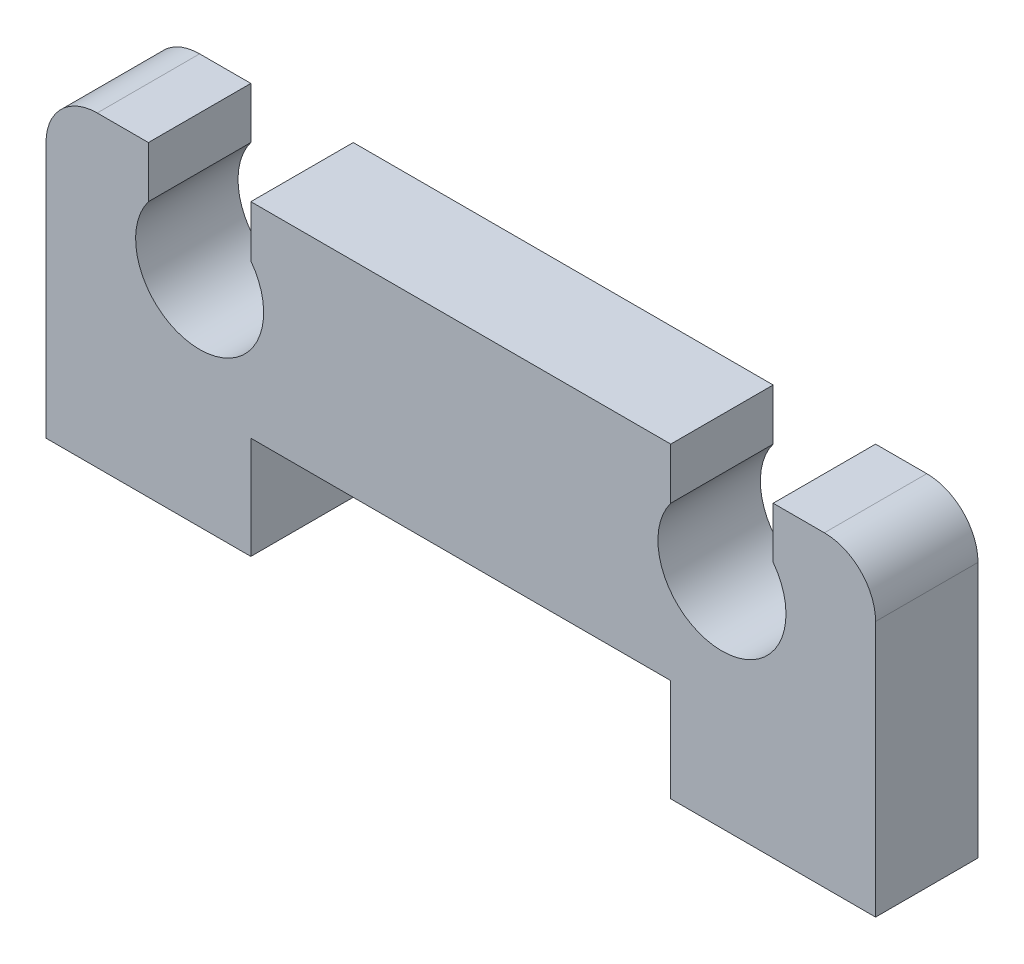
SolidWorks part; units mm, degrees
ref_plane "Front Plane" through (0, 0, 0) normal (0, 0, 1) x (1, 0, 0)
ref_plane "Top Plane" through (0, 0, 0) normal (0, 1, 0) x (1, 0, 0)
ref_plane "Right Plane" through (0, 0, 0) normal (1, 0, 0) x (0, 0, -1)
sketch "Sketch1" plane through (0, 0, 0) normal (0, 0, 1) x (1, 0, 0)
  line L0 (12.2, 2) -> (12.2, 0)
  line L1 (12.2, 6) -> (12.2, 5)
  line L2 (4, 2) -> (12.2, 2)
  line L3 (0, 0) -> (4, 0)
  line L4 (4, 0) -> (4, 2)
  line L5 (2, 6) -> (2, 5)
  line L6 (16.2, 0) -> (12.2, 0)
  line L7 (2, 6) -> (1, 6)
  line L8 (4, 6) -> (4, 5)
  line L9 (14.2, 6) -> (14.2, 5)
  line L10 (14.2, 6) -> (15.2, 6)
  line L11 (16.2, 5) -> (16.2, 0)
  line L12 (0, 0) -> (0, 5)
  line L13 (4, 6) -> (12.2, 6)
  arc A0 (16.2, 5) -> (15.2, 6) centre (15.2, 5) ccw
  arc A1 (2, 5) -> (4, 5) centre (3, 4.25) ccw
  arc A2 (12.2, 5) -> (14.2, 5) centre (13.2, 4.25) ccw
  arc A3 (1, 6) -> (0, 5) centre (1, 5) ccw
extrude "Boss-Extrude1" add sketch "Sketch1" along normal blind 2
